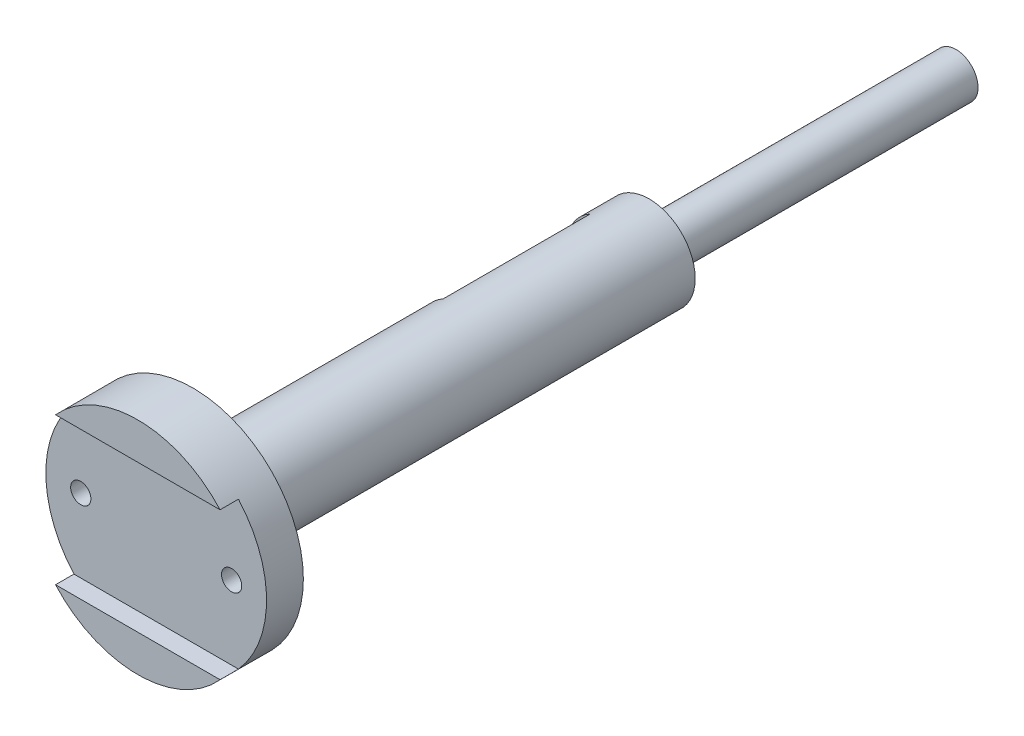
SolidWorks part; units mm, degrees
ref_plane "Plan de face" through (0, 0, 0) normal (0, 0, 1) x (1, 0, 0)
ref_plane "Plan de dessus" through (0, 0, 0) normal (0, 1, 0) x (1, 0, 0)
ref_plane "Plan de droite" through (0, 0, 0) normal (1, 0, 0) x (0, 0, -1)
sketch "Esquisse1" plane through (0, 0, 0) normal (0, 0, 1) x (1, 0, 0)
  circle A0 centre (0, 0) radius 30
  dimension "D1" = 60
extrude "Boss.-Extru.1" add sketch "Esquisse1" along normal blind 15
sketch "Esquisse2" plane through (0, 0, 0) normal (0, 0, -1) x (-1, 0, 0)
  circle A0 centre (0, 0) radius 12.5
  dimension "D1" = 25
extrude "Boss.-Extru.2" add sketch "Esquisse2" along normal blind 124
sketch "Esquisse4" plane through (0, 0, 15) normal (0, 0, 1) x (1, 0, 0)
  line L1 (115, 20) -> (-115, 20)
  line L2 (115, 20) -> (115, -20)
  line L3 (115, -20) -> (-115, -20)
  line L4 (-115, 20) -> (-115, -20)
  line L5 (115, 20) -> (-115, -20) construction
  line L6 (115, -20) -> (-115, 20) construction
  point P0 (0, 0)
  dimension "D1" = 40
  dimension "D2" = 230
extrude "Boss.-Extru.3" [suppressed] add sketch "Esquisse4" along normal blind 5
extrude "Enlèv. mat.-Extru.1" cut sketch "Esquisse4<2>" against normal blind 5
sketch "Esquisse4<2>" plane through (0, 0, 15) normal (0, 0, 1) x (1, 0, 0) same geometry as "Esquisse4"
sketch "Esquisse6" plane through (0, 0, 0) normal (0, 0, -1) x (-1, 0, 0)
  circle A2 centre (0, 0) radius 20.5
  circle A3 centre (0, 0) radius 20.5 construction
  dimension "D1" = 8
hole_wizard "Chambrage pour vis à tête hexagonale M51" positions "Esquisse15" profile "Esquisse14" counterbore size "M5" standard "Ansi Metric" end condition through all
sketch "Esquisse15" plane through (0, 0, 0) normal (0, 0, -1) x (-1, 0, 0)
  circle A0 centre (0, 0) radius 20.5 construction
  point P0 (20.5, 0)
  point P4 (-20.5, 0)
sketch "Esquisse14" plane through (-20.5, 0, 0) normal (1, 0, 0) x (0, 1, 0)
  line L0 (0, 0) -> (0, 15)
  line L1 (0, 15) -> (2.75, 15)
  line L2 (2.75, 3.605) -> (2.75, 15)
  line L3 (2.75, 3.605) -> (2.775, 3.58)
  line L4 (2.775, 3.58) -> (6.12, 3.58)
  line L5 (6.12, 3.58) -> (6.12, 0)
  line L7 (0, 0) -> (6.12, 0)
  line L9 (-2.75, 3.605) -> (-2.775, 3.58) construction
  line L11 (0, -6.35) -> (0, 107.95) construction
  dimension "Diamètre du perçage jusqu'au prochain" = 5.5
  dimension "Profondeur du perçage jusqu'au prochain" = 15
  dimension "Diamètre du chambrage" = 12.24
  dimension "Profondeur du chambrage" = 3.58
  dimension "Diamètre du fraisage milieu" = 5.55
  dimension "Angle du fraisage milieu" = 90
sketch "Esquisse17" plane through (0, 0, -124) normal (0, 0, -1) x (-1, 0, 0)
  circle A0 centre (0, 0) radius 6
  dimension "D1" = 12
extrude "Boss.-Extru.4" add sketch "Esquisse17" along normal blind 83.38
sketch "Esquisse18" plane through (0, 0, -207.38) normal (0, 0, -1) x (-1, 0, 0)
  line L0 (6.9654, 0) -> (-3.391, 0) construction
  line L1 (-3.391, 1.5) -> (6.9654, 1.5)
  line L2 (-3.391, 1.5) -> (-3.391, -1.5)
  line L3 (-3.391, -1.5) -> (6.9654, -1.5)
  line L4 (6.9654, 1.5) -> (6.9654, -1.5)
  line L5 (-3.391, 1.5) -> (6.9654, -1.5) construction
  line L6 (-3.391, -1.5) -> (6.9654, 1.5) construction
  point P0 (-0.771, 0)
  dimension "D1" = 3
  dimension "D2" = 2.62
extrude "Enlèv. mat.-Extru.2" cut sketch "Esquisse18" against normal blind 3
sketch "Esquisse19" plane through (0, 0, -124) normal (0, 0, -1) x (-1, 0, 0)
  line L0 (6, 10.9659) -> (6, -10.9659)
  line L1 (6, 10.9659) -> (13.9334, 10.9659)
  line L2 (6, -10.9659) -> (13.9334, -10.9659)
  line L3 (13.9334, 10.9659) -> (13.9334, -10.9659)
  circle A0 centre (0, 0) radius 12.5 construction
  circle A1 centre (0, 0) radius 12.5 construction
extrude "Enlèv. mat.-Extru.3" cut sketch "Esquisse19" against normal blind 50
sketch "Esquisse21" plane through (0, 0, -124) normal (0, 0, -1) x (-1, 0, 0)
  circle A0 centre (0, 0) radius 12.5
extrude "Boss.-Extru.6" add sketch "Esquisse21" against normal blind 10
